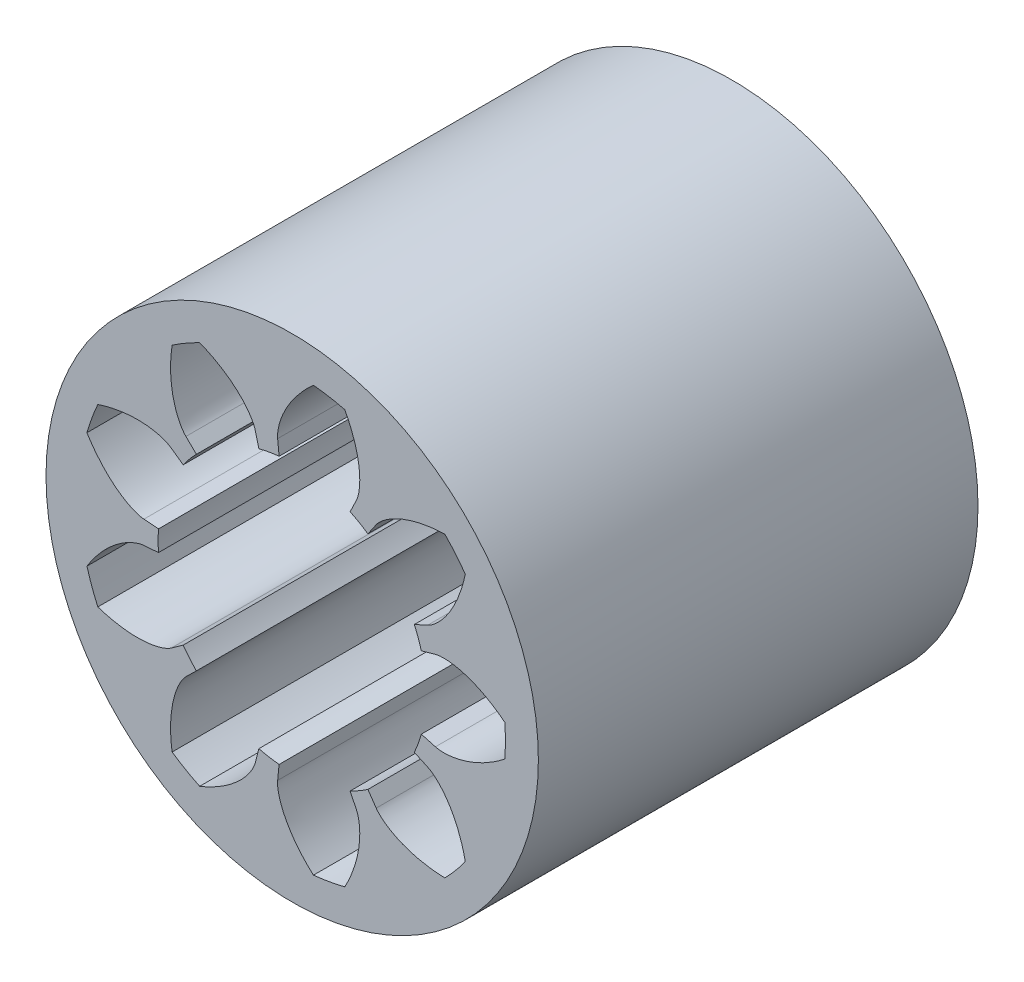
SolidWorks part; units mm, degrees
ref_plane "前视基准面" through (0, 0, 0) normal (0, 0, 1) x (1, 0, 0)
ref_plane "上视基准面" through (0, 0, 0) normal (0, 1, 0) x (1, 0, 0)
ref_plane "右视基准面" through (0, 0, 0) normal (1, 0, 0) x (0, 0, -1)
other "Configuration Table"
sketch "草图1" plane through (0, 0, 0) normal (0, 0, 1) x (1, 0, 0)
  line L0 (0, 0) -> (1.7387, 0.4659) construction
  line L1 (0, 0) -> (1.6291, 0.4551)
  line L2 (0, 0) -> (1.6291, -0.4551)
  line L3 (0, 0) -> (1.7387, -0.4659) construction
  line L4 (0, 0) -> (2.425, 0) construction
  line L5 (1.7387, 0.4659) -> (1.7387, -0.4659) construction
  circle A0 centre (0, 0) radius 1.525
  circle A1 centre (0, 0) radius 2.425
  circle A2 centre (0, 0) radius 1.6914 construction
  circle A3 centre (0, 0) radius 1.8 construction
  circle A4 centre (0, 0) radius 2.8
  spline S0 degree 4 poles (1.6291, 0.4551) (1.6415, 0.4586) (1.6769, 0.4656) (1.746, 0.4684) (1.8576, 0.4574) (1.9985, 0.4209) (2.171, 0.3489) (2.3582, 0.2351) (2.5438, 0.0819) (2.7191, -0.1093) (2.8693, -0.3205) (2.9946, -0.5472) (3.1006, -0.7975) (3.1986, -1.1195) (3.2658, -1.5159) (3.2754, -1.9832) (3.2064, -2.4974) (3.0631, -2.9965) (2.8558, -3.471) (2.5865, -3.9159) (2.2706, -4.3232) (1.901, -4.6937) (1.507, -5.0164) (1.0559, -5.3028) (0.6986, -5.4883) (0.2793, -5.6591) (0.0342, -5.7399) (-0.2484, -5.8241) (-0.3932, -5.8525) (-0.5197, -5.8826) (-0.5587, -5.8884) (-0.5863, -5.894) (-0.6011, -5.8971) knots 0 0 0 0 0 0.005604 0.015718 0.02996 0.048734 0.068727 0.096889 0.125051 0.153212 0.181374 0.209535 0.237696 0.271429 0.327752 0.384075 0.440398 0.496721 0.553044 0.609367 0.66569 0.722013 0.778336 0.834659 0.890982 0.909091 0.954545 0.977273 0.988636 0.994318 1 1 1 1 1 construction
  spline S1 degree 4 poles (1.6291, 0.4551) (1.6415, 0.4586) (1.6769, 0.4656) (1.746, 0.4684) (1.8576, 0.4574) (1.9985, 0.4209) (2.171, 0.3489) (2.3582, 0.2351) (2.5438, 0.0819) (2.7191, -0.1093) (2.8693, -0.3205) (2.9946, -0.5472) (3.1006, -0.7975) (3.1986, -1.1195) (3.2658, -1.5159) (3.2754, -1.9832) (3.2064, -2.4974) (3.0631, -2.9965) (2.8558, -3.471) (2.5865, -3.9159) (2.2706, -4.3232) (1.901, -4.6937) (1.507, -5.0164) (1.0559, -5.3028) (0.6986, -5.4883) (0.3874, -5.615) (0.2408, -5.6686) (0.2052, -5.6811) knots 0 0 0 0 0 0.005604 0.015718 0.02996 0.048734 0.068727 0.096889 0.125051 0.153212 0.181374 0.209535 0.237696 0.271429 0.327752 0.384075 0.440398 0.496721 0.553044 0.609367 0.66569 0.722013 0.778336 0.834659 0.890982 0.909091 0.909091 0.909091 0.909091 0.909091
  spline S2 degree 4 poles (1.6291, -0.4551) (1.6415, -0.4586) (1.6769, -0.4656) (1.746, -0.4684) (1.8576, -0.4574) (1.9985, -0.4209) (2.171, -0.3489) (2.3582, -0.2351) (2.5438, -0.0819) (2.7191, 0.1093) (2.8693, 0.3205) (2.9946, 0.5472) (3.1006, 0.7975) (3.1986, 1.1195) (3.2658, 1.5159) (3.2754, 1.9832) (3.2064, 2.4974) (3.0631, 2.9965) (2.8558, 3.471) (2.5865, 3.9159) (2.2706, 4.3232) (1.901, 4.6937) (1.507, 5.0164) (1.0559, 5.3028) (0.6986, 5.4883) (0.2793, 5.6591) (0.0342, 5.7399) (-0.2484, 5.8241) (-0.3932, 5.8525) (-0.5197, 5.8826) (-0.5587, 5.8884) (-0.5863, 5.894) (-0.6011, 5.8971) knots 0 0 0 0 0 0.005604 0.015718 0.02996 0.048734 0.068727 0.096889 0.125051 0.153212 0.181374 0.209535 0.237696 0.271429 0.327752 0.384075 0.440398 0.496721 0.553044 0.609367 0.66569 0.722013 0.778336 0.834659 0.890982 0.909091 0.954545 0.977273 0.988636 0.994318 1 1 1 1 1 construction
  spline S3 degree 4 poles (1.6291, -0.4551) (1.6415, -0.4586) (1.6769, -0.4656) (1.746, -0.4684) (1.8576, -0.4574) (1.9985, -0.4209) (2.171, -0.3489) (2.3582, -0.2351) (2.5438, -0.0819) (2.7191, 0.1093) (2.8693, 0.3205) (2.9946, 0.5472) (3.1006, 0.7975) (3.1986, 1.1195) (3.2658, 1.5159) (3.2754, 1.9832) (3.2064, 2.4974) (3.0631, 2.9965) (2.8558, 3.471) (2.5865, 3.9159) (2.2706, 4.3232) (1.901, 4.6937) (1.507, 5.0164) (1.0559, 5.3028) (0.6986, 5.4883) (0.3874, 5.615) (0.2408, 5.6686) (0.2052, 5.6811) knots 0 0 0 0 0 0.005604 0.015718 0.02996 0.048734 0.068727 0.096889 0.125051 0.153212 0.181374 0.209535 0.237696 0.271429 0.327752 0.384075 0.440398 0.496721 0.553044 0.609367 0.66569 0.722013 0.778336 0.834659 0.890982 0.909091 0.909091 0.909091 0.909091 0.909091
  point P16 (1.7387, 0)
  dimension "内啮合齿顶圆直径" = 3.05
  dimension "内啮合分度圆直径" = 3.6
  dimension "内啮合基圆直径" = 3.3829
  dimension "内啮合齿根圆直径" = 4.85
  dimension "外径" = 5.6
  dimension "渐开线镜像线夹角" = 15
extrude "凸台-拉伸1" add sketch "草图1" along normal blind 5 contours A4 | A0
extrude "切除-拉伸2" cut sketch "草图1<3>" along normal through all contours A0 S3 A1 S1 region at (1.9135, 0, 0)
sketch "草图1<3>" plane through (0, 0, 0) normal (0, 0, 1) x (1, 0, 0) same geometry as "草图1"
pattern_circular "阵列(圆周)1" count 9 over 360 about axis through (0, 0, 5) along (0, 0, 1) of "切除-拉伸2"
equation "\"m\"= 0.4'模数"
equation "\"z1\"= 6'外啮合齿轮数"
equation "\"a\"= 20度'压力角"
equation "\"z2\" = 9'内啮合齿轮数"
equation "\"hax\"= 1'齿顶高系数"
equation "\"cx\"= 0.25'顶隙系数"
equation "\"ha\"= \"hax\" * \"m\"'齿顶高"
equation "\"hf\"= ( \"hax\" + \"cx\" ) * \"m\"'齿根高"
equation "\"d1\"= \"m\" * \"z1\"'外啮合分度圆直径"
equation "\"da1\"= ( \"z1\" + 2 ) * \"m\"'外啮合齿顶圆直径"
equation "\"df1\"= \"d1\" - 2 * \"hf\"'外啮合齿根圆直径"
equation "\"db1\"= \"d1\" * cos ( \"a\" )'外啮合基圆直径"
equation "\"p\"= \"m\" * PI'齿距"
equation "\"d2\"= \"m\" * \"z2\"'内啮合分度圆直径"
equation "\"db2\"= \"d2\" * cos ( \"a\" )'内啮合基圆直径"
equation "\"da2\"= ( \"z2\" - 2 ) * \"m\"'内啮合齿顶圆直径"
equation "\"df2\"= \"d2\" + 2 * \"hf\"'内啮合齿根圆直径"
equation "\"内啮合齿顶圆直径@草图1\" = \"da2\" + 0.5 * \"hf\""
equation "\"内啮合齿根圆直径@草图1\"= \"df2\" + 0.5 * \"hf\""
equation "\"内啮合分度圆直径@草图1\"= \"d2\""
equation "\"内啮合基圆直径@草图1\"= \"db2\""
equation "\"渐开线镜像线夹角@草图1\"= 360度 / 4 / \"z2\" + 360度 / 4 / \"z2\" / 2"
equation "\"do\"= IIF ( \"edo\" >= ( \"df2\" + 1 ) , \"edo\" , ( \"df2\" + 1 ) )'外圈直径"
equation "\"h\"= 5'厚度"
equation "\"外径@草图1\"= \"do\""
equation "\"厚度@凸台-拉伸1\"= \"h\""
equation "\"内啮合齿轮数@阵列(圆周)1\"= \"z2\""
equation "\"edo\"= 3'期望的外圈直径"
